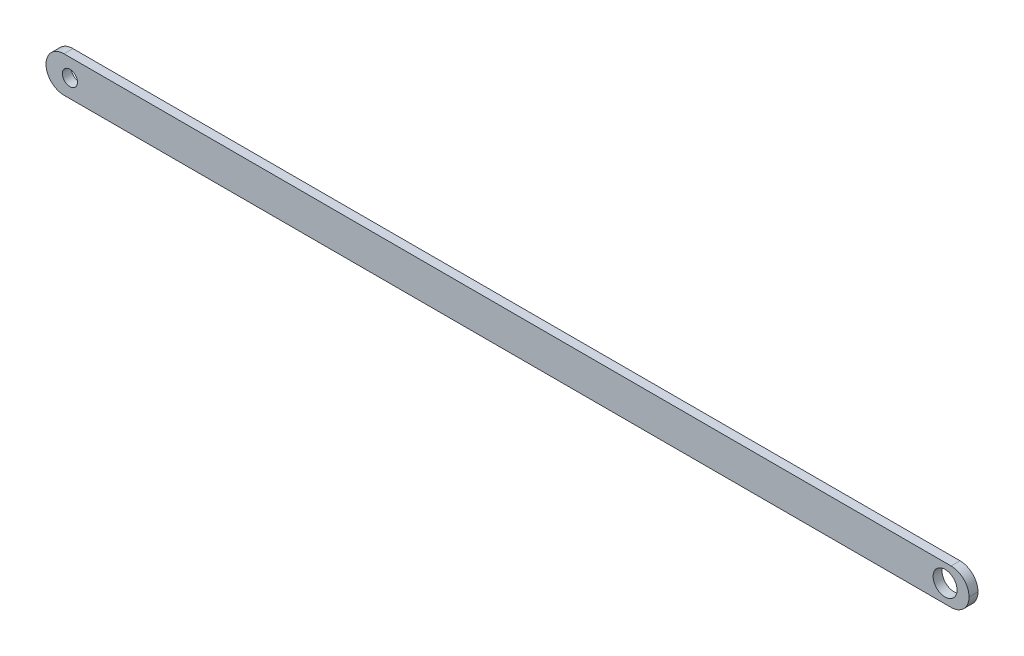
SolidWorks part; units mm, degrees
ref_plane "Front Plane" through (0, 0, 0) normal (0, 0, 1) x (1, 0, 0)
ref_plane "Top Plane" through (0, 0, 0) normal (0, 1, 0) x (1, 0, 0)
ref_plane "Right Plane" through (0, 0, 0) normal (1, 0, 0) x (0, 0, -1)
sketch "Sketch2" plane through (0, 0, 0) normal (0, 0, 1) x (1, 0, 0)
  line L1 (120.4296, 289.7111) -> (610.2396, 289.7111)
  line L2 (120.4296, 289.7111) -> (120.4296, 308.7611)
  line L3 (120.4296, 308.7611) -> (610.2396, 308.7611)
  line L4 (610.2396, 289.7111) -> (610.2396, 308.7611)
  circle A0 centre (133.1296, 299.2361) radius 4
  circle A1 centre (597.5396, 299.2361) radius 6.35
  dimension "D3" = 12.7
  dimension "D4" = 8
  dimension "D1" = 464.41
  dimension "D2" = 19.05
  dimension "D5" = 12.7
  dimension "D6" = 9.525
extrude "Boss-Extrude1" add sketch "Sketch2" along normal blind 4.7625
fillet "Fillet1" radius 9.525 4 edges at (610.2396, 308.7611, 2.3813) (610.2396, 289.7111, 2.3813) (120.4296, 289.7111, 2.3813) (120.4296, 308.7611, 2.3813)
